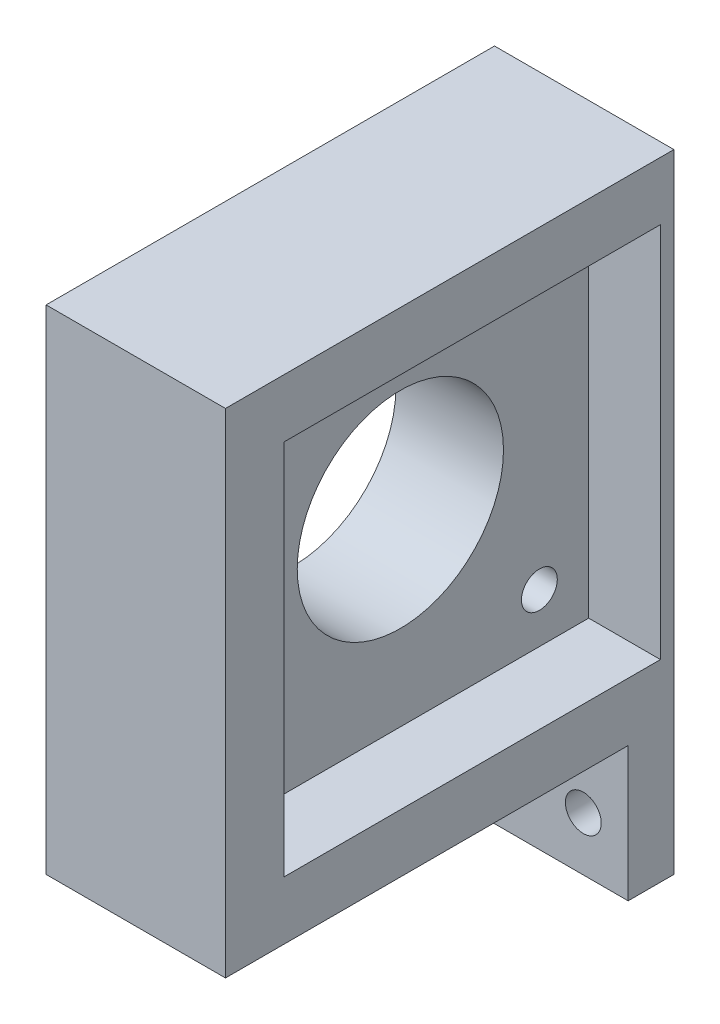
SolidWorks part; units mm, degrees
ref_plane "Front Plane" through (0, 0, 0) normal (0, 0, 1) x (1, 0, 0)
ref_plane "Top Plane" through (0, 0, 0) normal (0, 1, 0) x (1, 0, 0)
ref_plane "Right Plane" through (0, 0, 0) normal (1, 0, 0) x (0, 0, -1)
sketch "Sketch1" plane through (0, 0, 0) normal (0, 1, 0) x (1, 0, 0)
  line L1 (0, 0) -> (-20, 0)
  line L2 (0, 0) -> (0, -50)
  line L3 (0, -50) -> (-20, -50)
  line L4 (-20, 0) -> (-20, -50)
  dimension "D1" = 20
  dimension "D2" = 50
extrude "Boss-Extrude1" add sketch "Sketch1" along normal blind 70
sketch "Sketch2" plane through (0, 0, 0) normal (1, 0, 0) x (0, 0, -1)
  line L0 (-50, 70) -> (0, 70) construction
  line L1 (0, 70) -> (0, 0) construction
  line L2 (0, 42.5) -> (-50, 42.5) construction
  line L4 (-22.5, 70) -> (-22.5, 0) construction
  line L5 (-50, 0) -> (0, 0) construction
  line L7 (-50, 70) -> (-50, 0) construction
  circle A0 centre (-7, 58) radius 2
  circle A4 centre (-22.5, 42.5) radius 11.5
  circle A5 centre (-7, 27) radius 2
  circle A6 centre (-38, 27) radius 2
  circle A7 centre (-38, 58) radius 2
  dimension "D1" = 4
  dimension "D2" = 12
  dimension "D3" = 7
  dimension "D6" = 23
  dimension "D7" = 0
  dimension "D8" = 0
  dimension "D4" = 15.5
  dimension "D5" = 15.5
extrude "Cut-Extrude2" cut sketch "Sketch2" against normal blind 60
sketch "Sketch4" plane through (0, 0, 0) normal (1, 0, 0) x (0, 0, -1)
  line L1 (-50, 0) -> (-5.1, 0)
  line L2 (-50, 0) -> (-50, 15)
  line L3 (-50, 15) -> (-5.1, 15)
  line L4 (-5.1, 0) -> (-5.1, 15)
  circle A0 centre (-22.5, 42.5) radius 11.5 construction
  dimension "D1" = 15
  dimension "D2" = 17.4
extrude "Cut-Extrude3" cut sketch "Sketch4" against normal blind 60
sketch "Sketch8" plane through (0, 0, 0) normal (0, 0, -1) x (-1, 0, 0)
  line L0 (0, 0) -> (20, 0) construction
  line L1 (20, 70) -> (20, 0) construction
  circle A0 centre (15, 6) radius 2
  dimension "D1" = 4
  dimension "D2" = 6
  dimension "D3" = 5
extrude "Cut-Extrude5" cut sketch "Sketch8" against normal blind 15
sketch "Sketch9" plane through (0, 0, 0) normal (1, 0, 0) x (0, 0, -1)
  line L0 (0, 42.5) -> (-50, 42.5) construction
  line L1 (-1.5, 63.5) -> (-43.5, 63.5)
  line L2 (-1.5, 63.5) -> (-1.5, 21.5)
  line L3 (-1.5, 21.5) -> (-43.5, 21.5)
  line L4 (-43.5, 63.5) -> (-43.5, 21.5)
  line L5 (0, 70) -> (0, 0) construction
  line L6 (-50, 70) -> (-50, 15) construction
  line L7 (-22.5, 70) -> (-22.5, 15) construction
  line L8 (-50, 70) -> (0, 70) construction
  line L9 (-5.1, 15) -> (-50, 15) construction
  circle A0 centre (-22.5, 42.5) radius 11.5 construction
  dimension "D1" = 0
  dimension "D2" = 42
  dimension "D3" = 21
  dimension "D4" = 42
  dimension "D5" = 21
  dimension "D6" = 0
extrude "Cut-Extrude6" cut sketch "Sketch9" against normal blind 8
sketch "Sketch10" plane through (0, 0, 0) normal (0, 0, -1) x (-1, 0, 0)
  line L0 (0, 70) -> (0, 0) construction
  circle A0 centre (5, 6) radius 2
  circle A1 centre (15, 6) radius 2 construction
  dimension "D1" = 4
  dimension "D2" = 5
  dimension "D3" = 0
extrude "Cut-Extrude7" cut sketch "Sketch10" against normal blind 7
